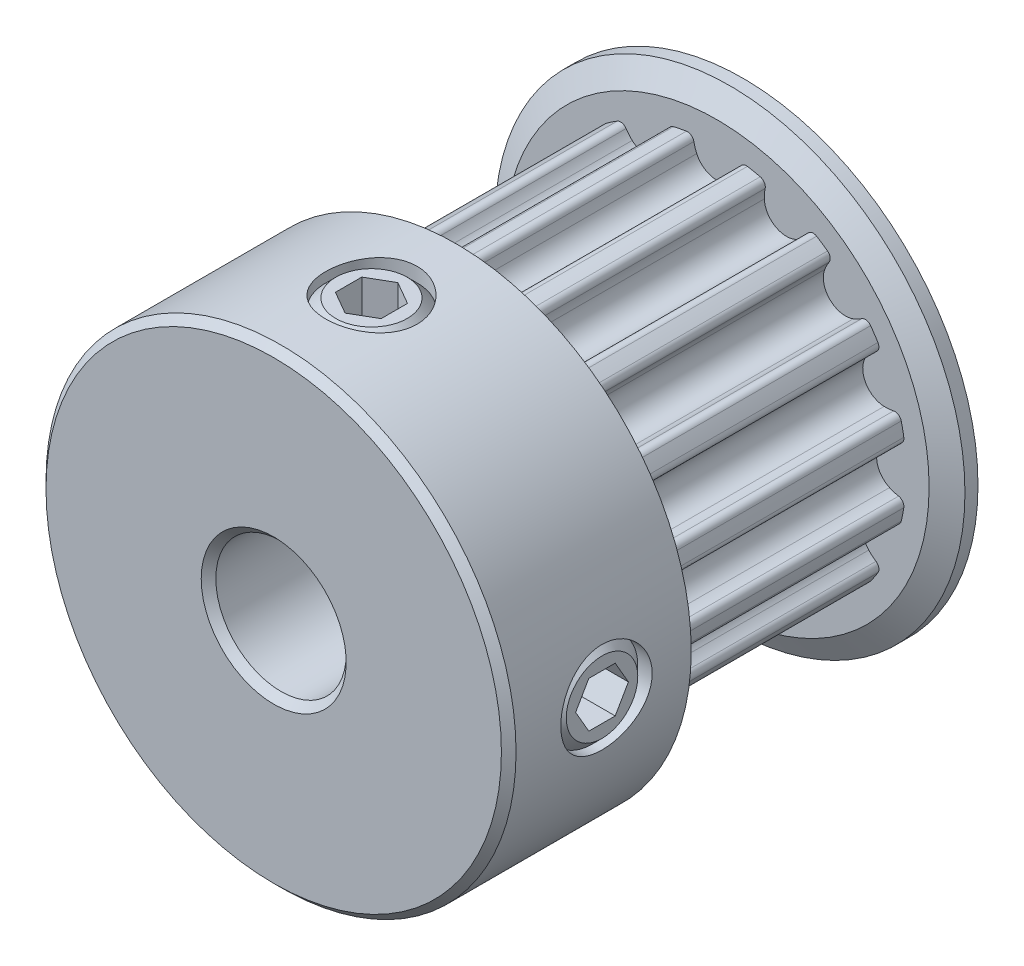
SolidWorks part; units mm, degrees
ref_plane "Front Plane" through (0, 0, 0) normal (0, 0, 1) x (1, 0, 0)
ref_plane "Top Plane" through (0, 0, 0) normal (0, 1, 0) x (1, 0, 0)
ref_plane "Right Plane" through (0, 0, 0) normal (1, 0, 0) x (0, 0, -1)
sketch "Sketch1" plane through (0, 0, 0) normal (0, 0, 1) x (1, 0, 0)
  line L1 (-2.553, 6.1245) -> (2.553, 6.1245) construction
  line L4 (0, 0) -> (0, 6.1245) construction
  line L5 (0, 6.1245) -> (0, 12.0664) construction
  line L6 (0, 7.6455) -> (2.9417, 7.0569) construction
  line L7 (2.9417, 7.0569) -> (3.8741, 6.6682) construction
  line L8 (2.9417, 7.0569) -> (2.553, 6.1245) construction
  line L9 (-2.9417, 7.0569) -> (-2.553, 6.1245) construction
  line L10 (-2.7951, 6.7052) -> (-3.7579, 9.015)
  line L11 (-3.7579, 9.015) -> (3.7579, 9.015)
  line L12 (3.7579, 9.015) -> (2.7951, 6.7052)
  circle A0 centre (0, 0) radius 7.6455 construction
  circle A1 centre (0, 0) radius 9.015 construction
  circle A2 centre (0, 0) radius 7.2645 construction
  arc A3 (-0.7739, 6.6229) -> (0.7739, 6.6229) centre (0, 6.9745) ccw
  arc A4 (-0.7739, 6.6229) -> (-0.8836, 6.9694) centre (0.61, 7.2516) cw
  arc A5 (-2.7951, 6.7052) -> (-1.1695, 7.1697) centre (0, 0) cw
  arc A6 (-0.8836, 6.9694) -> (-1.1695, 7.1697) centre (-1.1292, 6.923) ccw
  arc A7 (2.7951, 6.7052) -> (1.1695, 7.1697) centre (0, 0) ccw
  arc A8 (0.8836, 6.9694) -> (1.1695, 7.1697) centre (1.1292, 6.923) cw
  arc A9 (0.7739, 6.6229) -> (0.8836, 6.9694) centre (-0.61, 7.2516) ccw
  point P6 (0, 20.9083)
  point P11 (0, 7.6455)
  point P13 (0, 9.015)
  point P14 (0, 7.2645)
  dimension "D1" = 8.8419
  dimension "D2" = 4.4209
sketch "Sketch2" plane through (0, 0, 0) normal (1, 0, 0) x (0, 0, -1)
  line L0 (-9, 2.5) -> (9, 2.5)
  line L1 (-9, 2.5) -> (-9, 9.015)
  line L2 (-2, 9.015) -> (-9, 9.015)
  line L3 (-2.5, 2.5) -> (-2.5, 9.015) construction
  line L4 (-2.5, 9.015) -> (-1.5, 9.015) construction
  line L5 (-1.5, 9.015) -> (-1.5, 7.2645) construction
  line L6 (-1.5, 7.2645) -> (8, 7.2645)
  line L7 (8, 7.2645) -> (8, 9.015) construction
  line L8 (8, 9.015) -> (9, 9.015) construction
  line L9 (9, 9.015) -> (9, 2.5)
  line L10 (-9, 0) -> (9, 0) construction
  line L11 (8.5, 9.015) -> (8, 8.1398)
  line L12 (-1.5, 8.1398) -> (-2, 9.015)
  line L14 (-1.5, 8.1398) -> (-1.5, 7.2645)
  line L15 (8, 7.2645) -> (8, 8.1398)
  line L16 (8.5, 9.015) -> (9, 9.015)
  arc A0 (-1.5, 8.1398) -> (-2, 9.015) centre (-2.5161, 8.1398) ccw construction
  arc A1 (8, 8.1398) -> (8.5, 9.015) centre (9.0161, 8.1398) cw construction
  point P12 (-1.5, 8.1398)
  point P14 (-2, 9.015)
  point P20 (8, 8.1398)
  point P21 (8.5, 9.015)
  point P25 (8, 0)
  point P26 (-1.5, 0)
  dimension "D1" = 7.5
  dimension "OA" = 18
  dimension "Bore" = 5
  dimension "Inside Width" = 9.5
revolve "Revolve1" add sketch "Sketch2" angle 360 mid plane about L10
sketch "Sketch3" plane through (0, 0, 0) normal (0, 0, 1) x (1, 0, 0)
  line L6 (3.7579, 9.015) -> (-3.7579, 9.015)
  line L7 (2.7951, 6.7052) -> (3.7579, 9.015)
  line L8 (-3.7579, 9.015) -> (-2.7951, 6.7052)
  line L9 (3.7579, 9.015) -> (-3.7579, 9.015)
  line L10 (2.7951, 6.7052) -> (3.7579, 9.015)
  line L11 (-3.7579, 9.015) -> (-2.7951, 6.7052)
  arc A8 (2.7951, 6.7052) -> (1.1695, 7.1697) centre (0, 0) ccw
  arc A9 (1.1695, 7.1697) -> (0.8836, 6.9694) centre (1.1292, 6.923) ccw
  arc A10 (0.7739, 6.6229) -> (0.8836, 6.9694) centre (-0.61, 7.2516) ccw
  arc A11 (-0.7739, 6.6229) -> (0.7739, 6.6229) centre (0, 6.9745) ccw
  arc A12 (-0.8836, 6.9694) -> (-0.7739, 6.6229) centre (0.61, 7.2516) ccw
  arc A13 (-0.8836, 6.9694) -> (-1.1695, 7.1697) centre (-1.1292, 6.923) ccw
  arc A14 (-1.1695, 7.1697) -> (-2.7951, 6.7052) centre (0, 0) ccw
  arc A15 (2.7951, 6.7052) -> (1.1695, 7.1697) centre (0, 0) ccw
  arc A16 (1.1695, 7.1697) -> (0.8836, 6.9694) centre (1.1292, 6.923) ccw
  arc A17 (0.7739, 6.6229) -> (0.8836, 6.9694) centre (-0.61, 7.2516) ccw
  arc A18 (-0.7739, 6.6229) -> (0.7739, 6.6229) centre (0, 6.9745) ccw
  arc A19 (-0.8836, 6.9694) -> (-0.7739, 6.6229) centre (0.61, 7.2516) ccw
  arc A20 (-0.8836, 6.9694) -> (-1.1695, 7.1697) centre (-1.1292, 6.923) ccw
  arc A21 (-1.1695, 7.1697) -> (-2.7951, 6.7052) centre (0, 0) ccw
  dimension "D1" = 0
extrude "Cut-Extrude1" cut sketch "Sketch3" against normal up to vertex (8 mm away) from vertex up to point (0, 7.2645, -8) starting at point (0, 7.2645, 1.5)
pattern_circular "CirPattern1" count 16 over 360 about axis through (0, 0, 9) along (0, 0, 1) of "Cut-Extrude1"
sketch "Sketch4" plane through (0, 0, 0) normal (1, 0, 0) x (0, -1, 0)
  line L0 (0, -1.5) -> (0, -9) construction
  line L1 (-2.5, -9) -> (2.5, -9) construction
  line L2 (8.1398, -1.5) -> (-8.1398, -1.5) construction
  circle A0 centre (0, -5.25) radius 1.7526
extrude "Cut-Extrude2" cut sketch "Sketch4" along normal through all
ref_plane "Plane1" through (0, 0, 5.25) normal (0, 0, 1) x (1, 0, 0)
sketch "Sketch5" plane through (0, 0, 5.25) normal (0, 0, 1) x (1, 0, 0)
  line L0 (0, 0) -> (0, 9.015) construction
  line L1 (2.5, -1.3716) -> (2.5, 0)
  line L2 (2.881, -1.7526) -> (8.462, -1.7526)
  line L3 (2.5, 0) -> (9.015, 0) construction
  line L4 (2.5, 0) -> (8.843, 0)
  line L5 (8.843, 0) -> (8.843, -1.3716)
  line L6 (2.881, -1.7526) -> (2.5, -1.3716)
  line L7 (8.843, -1.3716) -> (8.462, -1.7526)
  circle A0 centre (0, 0) radius 9.015 construction
  circle A1 centre (0, 0) radius 2.5 construction
  point P2 (2.5, -1.7526)
  point P11 (8.843, -1.7526)
revolve "Revolve2" add sketch "Sketch5" angle 360 mid plane about L4
sketch "Sketch6" plane through (8.843, 5.3841, 0) normal (-1, 0, 0) x (0, -1, 0)
  line L1 (5.3841, 6.2619) -> (4.5078, 5.7559)
  line L2 (4.5078, 5.7559) -> (4.5078, 4.7441)
  line L3 (4.5078, 4.7441) -> (5.3841, 4.2381)
  line L4 (5.3841, 4.2381) -> (6.2604, 4.7441)
  line L5 (6.2604, 4.7441) -> (6.2604, 5.7559)
  line L6 (6.2604, 5.7559) -> (5.3841, 6.2619)
  circle A0 centre (5.3841, 5.25) radius 0.8763 construction
  dimension "D1" = 1.7526
extrude "Cut-Extrude3" cut sketch "Sketch6" along normal blind 1.3144
pattern_circular "CirPattern3" count 2 over 90 about axis through (0, 0, 9) along (0, 0, 1) of "Cut-Extrude2", "Revolve2", "Cut-Extrude3"
chamfer "Chamfer1" distance 0.2807 angle 45 2 edges at (2.5, 0, 9) (9.015, 0, 9)
ref_axis "Center Axis 1" through (0, 0, -9) along (0, 0, 1)
ref_plane "Contact Plane 1" through (0, 0, 9) normal (0, 0, 1) x (1, 0, 0)
ref_plane "Contact Plane 2" through (0, 0, -9) normal (0, 0, -1) x (-1, 0, 0)
equation "\"D2@Sketch1\"= \"D1@Sketch1\" / 2"
equation "\"D1@Sketch6\" = \"Set Screw@Sketch4\" / 2"
equation "\"D1@Cut-Extrude3\" = \"D1@Sketch6\"*.75"
